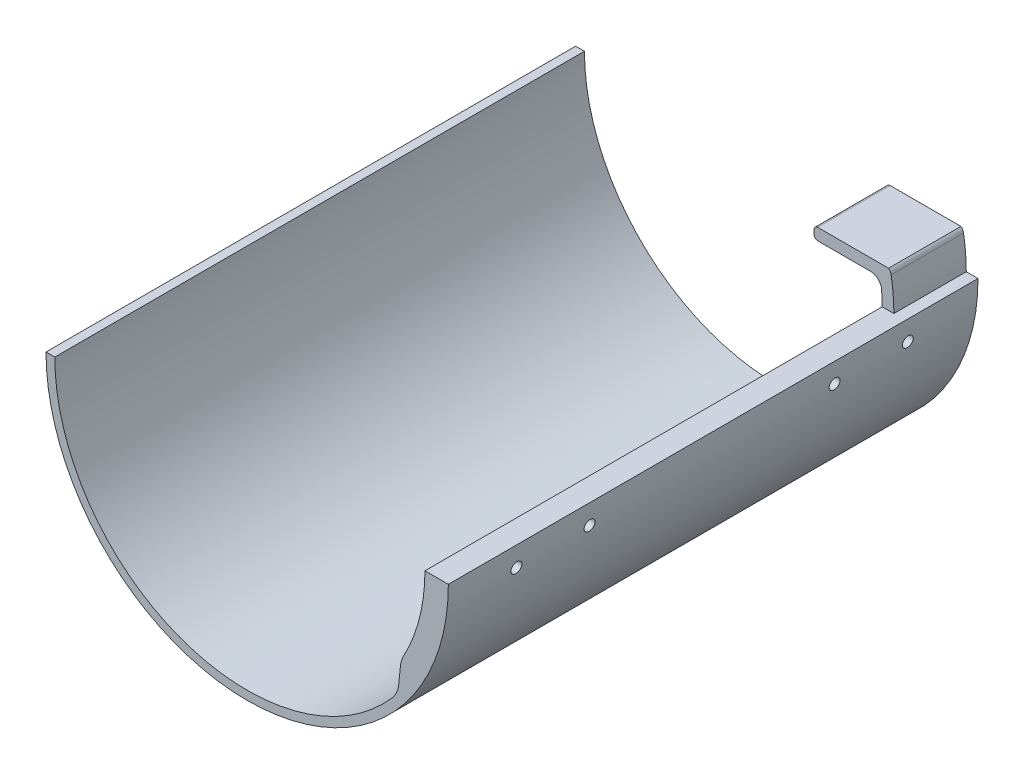
SolidWorks part; units mm, degrees
ref_plane "前视基准面" through (0, 0, 0) normal (0, 0, 1) x (1, 0, 0)
ref_plane "上视基准面" through (0, 0, 0) normal (0, 1, 0) x (1, 0, 0)
ref_plane "右视基准面" through (0, 0, 0) normal (1, 0, 0) x (0, 0, -1)
other "Configuration Table"
sketch "草图1" plane through (0, 0, 0) normal (0, 0, 1) x (1, 0, 0)
  line L0 (-55, 0) -> (-52.6, 0)
  line L1 (51.8, 0) -> (55, 0)
  line L2 (-52.6, 0) -> (51.8, 0) construction
  line L5 (41.9103, -25.796) -> (41.4208, -30.58)
  line L6 (0, 0) -> (0, 10) construction
  line L7 (0, 10) -> (31, 10) construction
  line L9 (30, 9) -> (30, 7.8)
  line L10 (31, 6.8) -> (45.4414, 6.8)
  line L11 (31, 10) -> (50.344, 10)
  arc A0 (-55, 0) -> (55, 0) centre (0, 0) ccw
  arc A1 (-52.6, 0) -> (39.7466, -34.4524) centre (0, 0) ccw
  arc A2 (51.0485, 8.7916) -> (51.8, 0) centre (0, 0) cw
  arc A3 (42.7207, -23.1711) -> (48.431, 4.05) centre (0, 0) ccw
  arc A4 (41.4208, -30.58) -> (39.7466, -34.4524) centre (34.4571, -29.8675) cw
  arc A5 (41.9103, -25.796) -> (42.7207, -23.1711) centre (48.8739, -26.5085) cw
  arc A6 (48.431, 4.05) -> (45.4414, 6.8) centre (45.4414, 3.8) ccw
  arc A7 (51.0485, 8.7916) -> (50.344, 10) centre (49.0775, 8.4521) ccw
  arc A8 (31, 6.8) -> (30, 7.8) centre (31, 7.8) cw
  arc A9 (30, 9) -> (31, 10) centre (31, 9) cw
  point P16 (42.0579, -24.3536)
  point P25 (52.0183, 10)
  point P28 (30, 6.8)
  point P31 (30.5845, 10)
  dimension "D1" = 110
  dimension "D2" = 105.2
  dimension "D3" = 97.2
  dimension "D6" = 7
  dimension "D9" = 3
  dimension "D10" = 2
  dimension "D11" = 1
  dimension "D12" = 1
  dimension "D14" = 51.8
  dimension "D5" = 31
  dimension "D7" = 3.2
  dimension "D8" = 21.4339
  dimension "D13" = 10
extrude "凸台-拉伸1" add sketch "草图1" along normal blind 144.8
sketch "草图4" plane through (0, 0, 144.8) normal (0, 0, 1) x (1, 0, 0)
  line L0 (55, 0) -> (0, 0)
  line L1 (0, 0) -> (50.017, 22.8758)
  arc A0 (55, 0) -> (50.017, 22.8758) centre (0, 0) ccw
sketch "草图5" plane through (0, 0, 0) normal (0, 0, -1) x (-1, 0, 0)
  line L0 (0, 0) -> (0, -5.5)
  line L1 (0, -5.5) -> (54.3615, -5.5)
  line L2 (0, 0) -> (54.3615, -5.5) construction
  line L3 (0, 0) -> (5.5, 54.3615) construction
  line L4 (0, 0) -> (0, 54.639) construction
  line L5 (0, 0) -> (-54.3615, -5.5) construction
  line L6 (0, 0) -> (-5.5, 54.3615) construction
  circle A0 centre (0, 0) radius 54.639
  dimension "D1" = 5.5
  dimension "D2" = 90
ref_plane "基准面1" through (0, 0, 0) normal (-0.9949, 0.1007, 0) x (0.1007, 0.9949, 0)
sketch "草图7" plane through (0, 0, 0) normal (-0.9949, 0.1007, 0) x (0.1007, 0.9949, 0)
  line L0 (-5.5363, -144.8) -> (-5.5363, 0) construction
  line L1 (-55, -144.8) -> (5.5363, -144.8) construction
  line L2 (-0.1363, 0) -> (-0.1363, -144.8) construction
  line L3 (54.639, 0) -> (-54.639, 0) construction
  line L4 (-5.4721, 0) -> (-10.9441, 0) construction
  circle A0 centre (-0.1363, -18.9) radius 1.5
  circle A1 centre (-0.1363, -38.9) radius 1.5
  circle A2 centre (-0.1363, -105.9) radius 1.5
  circle A3 centre (-0.1363, -125.9) radius 1.5
  dimension "D1" = 3
  dimension "D2" = 3
  dimension "D3" = 3
  dimension "D4" = 3
  dimension "D5" = 5.4
  dimension "D6" = 18.9
  dimension "D7" = 20
  dimension "D8" = 18.9
  dimension "D9" = 20
extrude "切除-拉伸6" cut sketch "草图7" against normal blind 80
sketch "草图8" plane through (0, 0, 0) normal (0, 0, -1) x (-1, 0, 0)
  line L0 (-50.017, 22.8758) -> (0, 0)
  line L1 (0, 0) -> (-55, 0)
  arc A0 (-55, 0) -> (-50.017, 22.8758) centre (0, 0) cw
  arc A1 (-50.017, 22.8758) -> (-55, 0) centre (0, 0) ccw construction
extrude "切除-拉伸8" cut sketch "草图4" against normal blind 125
